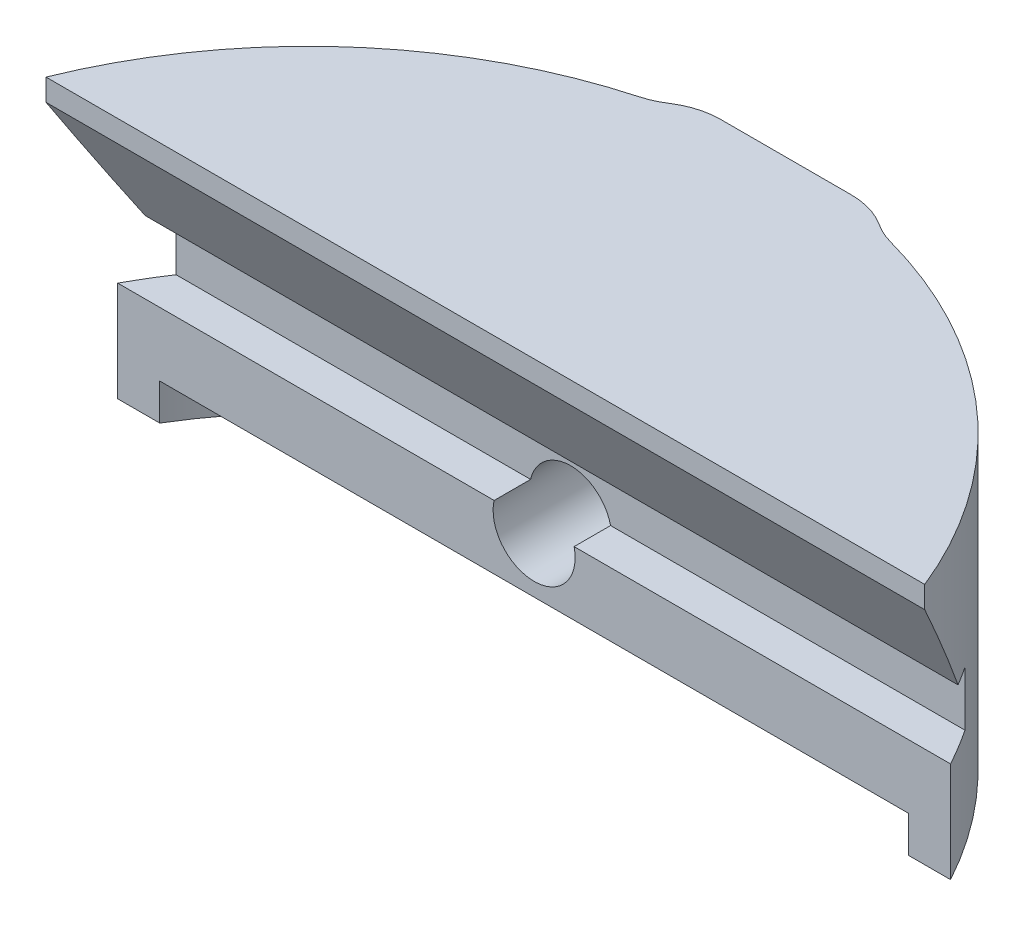
SolidWorks part; units mm, degrees
material "3.1355 (EN-AW 2024)"
ref_plane "Спереди" through (0, 0, 0) normal (0, 0, 1) x (1, 0, 0)
ref_plane "Сверху" through (0, 0, 0) normal (0, 1, 0) x (1, 0, 0)
ref_plane "Справа" through (0, 0, 0) normal (1, 0, 0) x (0, 0, -1)
sketch "Эскиз1" plane through (0, 0, 0) normal (0, 1, 0) x (1, 0, 0)
  circle A0 centre (0, 0) radius 26
  dimension "D1" = 52
extrude "Бобышка-Вытянуть1" add sketch "Эскиз1" along normal blind 14
sketch "Эскиз2" plane through (0, 0, 0) normal (1, 0, 0) x (0, 0, -1)
  line L0 (0, 14) -> (0, 0) construction
  line L1 (26, 14) -> (-26, 14) construction
  line L2 (13.6547, 6) -> (-13.6547, 6)
  line L3 (-13.6547, 6) -> (-9.7287, 12.8)
  line L4 (-9.7287, 12.8) -> (-9.7287, 14)
  line L5 (-9.7287, 14) -> (9.7287, 14)
  line L6 (0, 14) -> (0, 6) construction
  line L7 (13.6547, 6) -> (9.7287, 12.8)
  line L8 (9.7287, 12.8) -> (9.7287, 14)
  line L9 (-12.5, 8) -> (-12.5, 6) construction
  dimension "D1" = 8
  dimension "D2" = 1.2
  dimension "D3" = 60
  dimension "D4" = 13.6547
  dimension "D5" = 9.7287
  dimension "D6" = 2
  dimension "D7" = 12.5
extrude "Вырез-Вытянуть1" cut sketch "Эскиз2" against normal mid plane 60
sketch "Примерка" plane through (0, 0, 0) normal (1, 0, 0) x (0, 0, -1)
  line L0 (13.6547, 6) -> (-13.6547, 6) construction
  line L1 (-12.5, 14) -> (12.5, 14)
  line L2 (-12.5, 14) -> (-12.5, 6)
  line L3 (-12.5, 6) -> (12.5, 6)
  line L4 (12.5, 14) -> (12.5, 6)
  point P6 (0, 6)
  dimension "D1" = 8
  dimension "D2" = 25
sketch "Эскиз5" plane through (0, 0, 0) normal (0, -1, 0) x (1, 0, 0)
  line L2 (-22.1258, -15.6547) -> (22.1258, -15.6547)
  line L3 (-18.1915, -15.6547) -> (18.1915, -15.6547)
  circle A2 centre (0, 0) radius 24
  arc A3 (-18.1915, -15.6547) -> (18.1915, -15.6547) centre (0, 0) ccw
  dimension "D1" = 2
  dimension "D2" = 2
sketch "Эскиз6" plane through (0, 6, 0) normal (0, 1, 0) x (1, 0, 0)
  line L1 (18.4208, 0) -> (-15.4735, 0) construction
  circle A0 centre (0, 0) radius 6 construction
  circle A1 centre (0, 0) radius 12.5 construction
  dimension "D1" = 12
  dimension "D2" = 25
hole_wizard "Цековка для винта с внутренним шестигранником M32" positions "Эскиз14" profile "Эскиз13" counterbore size "M3" standard "Ansi Metric" end condition up to next
sketch "Эскиз14" plane through (0, 6, 0) normal (0, 1, 0) x (1, 0, 0)
  line L0 (18.4208, 0) -> (-15.4735, 0) construction
  circle A0 centre (0, 0) radius 12.5 construction
  circle A1 centre (0, 0) radius 6 construction
  point P0 (-12.5, 0)
  point P6 (12.5, 0)
  point P20 (-6, 0)
  point P24 (6, 0)
sketch "Эскиз13" plane through (-12.5, 6, 0) normal (1, 0, 0) x (0, 0, 1)
  line L0 (0, 0) -> (0, 6)
  line L1 (0, 6) -> (1.7, 6)
  line L3 (1.7, 6) -> (1.7, 3)
  line L4 (1.7, 3) -> (3.3, 3)
  line L5 (3.3, 3) -> (3.3, 0)
  line L7 (3.3, 0) -> (0, 0)
  line L11 (0, -6.35) -> (0, 107.95) construction
  dimension "Диаметр сквозного отверстия" = 3.4
  dimension "Глубина сквозного отверстия" = 6
  dimension "Диаметр цековки" = 6.6
  dimension "Глубина цековки" = 3
sketch "Эскиз12" plane through (0, 0, 0) normal (0, -1, 0) x (1, 0, 0)
  circle A0 centre (0, 0) radius 26 construction
  circle A1 centre (0, 0) radius 26
  circle A3 centre (0, 0) radius 24
  dimension "D1" = 2
extrude "Бобышка-Вытянуть2" add sketch "Эскиз12" along normal blind 2
sketch "Эскиз17" plane through (0, 14, 0) normal (0, 1, 0) x (1, 0, 0)
  line L0 (-24.1112, -9.7287) -> (24.1112, -9.7287) construction
  line L1 (-24.1112, -9.7287) -> (24.1112, -9.7287)
  arc A0 (-24.1112, -9.7287) -> (24.1112, -9.7287) centre (0, 0) ccw construction
  arc A1 (-24.1112, -9.7287) -> (24.1112, -9.7287) centre (0, 0) ccw
extrude "Вырез-Вытянуть4" cut sketch "Эскиз17" against normal up to surface (8 mm away) up to face at (9.25, 6, 0)
fillet "Скругление2" radius 1 4 edges at (9.25, 4.5, -0.5723) (9.25, 4.5, 0.5723) (-9.25, 4.5, 0.5723) (-9.25, 4.5, -0.5723)
sketch "Эскиз18" plane through (0, 0, 0) normal (0, -1, 0) x (1, 0, 0)
  circle A0 centre (0, 0) radius 6
extrude "Вырез-Вытянуть5" cut sketch "Эскиз18" against normal blind 3
sketch "Эскиз19" plane through (0, 6, 0) normal (0, 1, 0) x (1, 0, 0)
  line L0 (-22.3137, -13.3453) -> (22.3137, -13.3453)
  line L1 (-22.1258, 13.6547) -> (22.1258, 13.6547) construction
  arc A0 (-22.1258, 13.6547) -> (22.1258, 13.6547) centre (0, 0) ccw construction
  arc A1 (-22.3137, -13.3453) -> (22.3137, -13.3453) centre (0, 0) ccw
  dimension "D1" = 27
extrude "Вырез-Вытянуть6" cut sketch "Эскиз19" against normal blind 10
sketch "Эскиз21" plane through (0, 0, 13.3453) normal (0, 0, 1) x (1, 0, 0)
  line L0 (0, 0) -> (0, 6) construction
  line L1 (19.9475, 0) -> (-19.9475, 0) construction
  line L2 (22.3137, 6) -> (-22.3137, 6) construction
hole_wizard "Отверстие обработанное метчиком M4x0.71" positions "Эскиз23" profile "Эскиз22" tap size "M4x0.7" standard "Ansi Metric"
sketch "Эскиз23" plane through (0, 0, 13.3453) normal (0, 0, 1) x (1, 0, 0)
  line L0 (0, 0) -> (0, 6) construction
  point P0 (0, 3)
sketch "Эскиз22" plane through (0, 3, 13.3453) normal (1, 0, 0) x (0, -1, 0)
  line L0 (0, 0) -> (0, 12.4914)
  line L1 (0, 12.4914) -> (1.65, 11.5)
  line L2 (1.65, 11.5) -> (1.65, 0)
  line L5 (1.65, 0) -> (0, 0)
  line L10 (0, 12.4914) -> (-1.65, 11.5) construction
  line L11 (0, -6.35) -> (0, 107.95) construction
  dimension "Диаметр сверла" = 3.3
  dimension "Глубина сверла" = 11.5
  dimension "Угол заточки сверла" = 118
cosmetic thread "Отверстие резьбы1" parameters "D1"=8, "D2"=4
sketch "Эскиз20" plane through (0, 0, 13.3453) normal (0, 0, 1) x (1, 0, 0)
  line L0 (0, 3.1198) -> (0, -5.6063) construction
  line L1 (22.3137, 6) -> (-22.3137, 6) construction
  line L2 (-25.2658, 5) -> (25.2658, 5)
  line L3 (-25.2658, 5) -> (-25.2658, -2)
  line L4 (-25.2658, -2) -> (25.2658, -2)
  line L5 (25.2658, 5) -> (25.2658, -2)
  line L6 (-25.2658, 5) -> (25.2658, -2) construction
  line L7 (-25.2658, -2) -> (25.2658, 5) construction
  line L8 (-22.3137, -2) -> (-19.9475, -2) construction
  point P3 (0, 1.5)
  dimension "D1" = 1
extrude "Вырез-Вытянуть7" cut sketch "Эскиз20" against normal blind 2
sketch "Эскиз24" plane through (0, 0, 11.3453) normal (0, 0, 1) x (1, 0, 0)
  line L0 (0, 0) -> (0, -5.889) construction
  line L1 (-21.1491, 0) -> (21.1491, 0) construction
  line L2 (-11.3153, 1) -> (11.3153, 1)
  line L3 (-11.3153, 1) -> (-11.3153, 0)
  line L4 (-11.3153, 0) -> (11.3153, 0)
  line L5 (11.3153, 1) -> (11.3153, 0)
  line L6 (-11.3153, 1) -> (11.3153, 0) construction
  line L7 (-11.3153, 0) -> (11.3153, 1) construction
  point P3 (0, 0.5)
  dimension "D1" = 1
extrude "Бобышка-Вытянуть3" add sketch "Эскиз24" along normal blind 2
ref_plane "Плоскость1" through (26, 0, 0) normal (1, 0, 0) x (0, 0, -1)
sketch "Эскиз25" plane through (26, 0, 0) normal (1, 0, 0) x (0, 0, -1)
  line L0 (13.6547, 6) -> (13.6547, -5.3122) construction
  line L1 (12.4047, -5.3122) -> (-15.3444, -5.3122)
  line L2 (-15.3444, -5.3122) -> (-15.3444, 6)
  line L3 (-15.3444, 6) -> (12.4047, 6)
  line L4 (12.4047, 6) -> (12.4047, -5.3122)
  line L5 (13.6547, 6) -> (-13.3453, 6) construction
  dimension "D1" = 2.5
extrude "Вырез-Вытянуть8" cut sketch "Эскиз25" against normal through all
sketch "Эскиз26" plane through (26, 0, 0) normal (1, 0, 0) x (0, 0, -1)
  line L0 (12.4047, 6.5) -> (14.4047, 6.5)
  line L1 (14.4047, 6.5) -> (14.4047, 3.5)
  line L2 (14.4047, 3.5) -> (12.4047, 3.5)
  line L3 (12.4047, 3.5) -> (12.4047, 6.5)
  line L4 (12.4047, -2) -> (26, -2) construction
  line L7 (12.4047, 6) -> (12.4047, -2) construction
  dimension "D1" = 2
  dimension "D2" = 5.5
  dimension "D3" = 3
extrude "Вырез-Вытянуть10" cut sketch "Эскиз26" against normal through all
sketch "Эскиз27" plane through (0, 14, 0) normal (0, 1, 0) x (1, 0, 0)
  line L0 (0, 26) -> (0, 26.4574) construction
  line L2 (24.1112, 9.7287) -> (-24.1112, 9.7287) construction
  line L3 (-5, 26.2287) -> (5, 26.2287)
  line L4 (-5, 26.2287) -> (-5, 25.5147)
  line L6 (5, 26.2287) -> (5, 25.5147)
  line L7 (-5, 26.2287) -> (5.2086, 22.8067) construction
  line L8 (-6.2536, 22.4564) -> (5, 26.2287) construction
  arc A0 (-5, 25.5147) -> (5, 25.5147) centre (0, 0) cw
  arc A1 (24.1112, 9.7287) -> (-24.1112, 9.7287) centre (0, 0) ccw construction
  point P5 (0, 24.5527)
  point P18 (0, 26.2287)
  dimension "D1" = 10
  dimension "D2" = 16.5
extrude "Бобышка-Вытянуть5" add sketch "Эскиз27" against normal up to surface (16 mm away) up to face at (0, -2, -18.7024)
fillet "Скругление3" radius 4 2 edges at (5, 6, -25.5147) (-5, 6, -25.5147)
fillet "Скругление4" radius 4 2 edges at (5, 6, -26.2287) (-5, 6, -26.2287)
sketch "Эскиз28" plane through (0, 0, -26.2287) normal (0, 0, -1) x (-1, 0, 0)
  line L0 (0, -2) -> (0, 4.3259) construction
  line L1 (-3.5784, -2) -> (3.5784, -2) construction
  point P5 (0, 3)
  dimension "D1" = 5
hole_wizard "Отверстие с зазором M41" positions "Эскиз30" profile "Эскиз29" hole size "M4" standard "Ansi Metric" end condition through all
sketch "Эскиз30" plane through (0, 0, -26.2287) normal (0, 0, -1) x (-1, 0, 0)
  point P0 (0, 3)
sketch "Эскиз29" plane through (0, 3, -26.2287) normal (1, 0, 0) x (0, 1, 0)
  line L0 (0, 0) -> (0, 16.5)
  line L1 (0, 16.5) -> (2.25, 16.5)
  line L2 (2.25, 16.5) -> (2.25, 0)
  line L5 (2.25, 0) -> (0, 0)
  line L11 (0, -6.35) -> (0, 107.95) construction
  dimension "Диаметр сквозного отверстия" = 4.5
  dimension "Глубина сквозного отверстия" = 16.5
